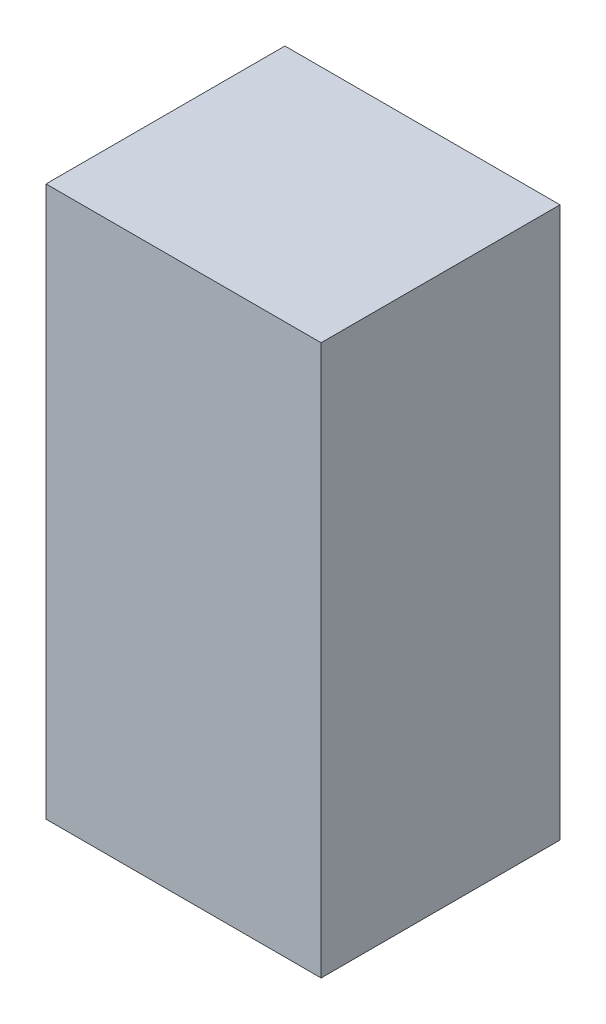
SolidWorks part; units mm, degrees
material "PTFE (general)"
ref_plane "Front Plane" through (0, 0, 0) normal (0, 0, 1) x (1, 0, 0)
ref_plane "Top Plane" through (0, 0, 0) normal (0, 1, 0) x (1, 0, 0)
ref_plane "Right Plane" through (0, 0, 0) normal (1, 0, 0) x (0, 0, -1)
sketch "Sketch1" plane through (0, 0, 0) normal (0, 1, 0) x (1, 0, 0)
  line L1 (-19, -16.5) -> (19, -16.5)
  line L2 (-19, -16.5) -> (-19, 16.5)
  line L3 (-19, 16.5) -> (19, 16.5)
  line L4 (19, -16.5) -> (19, 16.5)
  line L5 (-19, -16.5) -> (19, 16.5) construction
  line L6 (-19, 16.5) -> (19, -16.5) construction
  point P0 (0, 0)
  dimension "D1" = 33
  dimension "D2" = 38
extrude "Boss-Extrude1" add sketch "Sketch1" along normal blind 76
